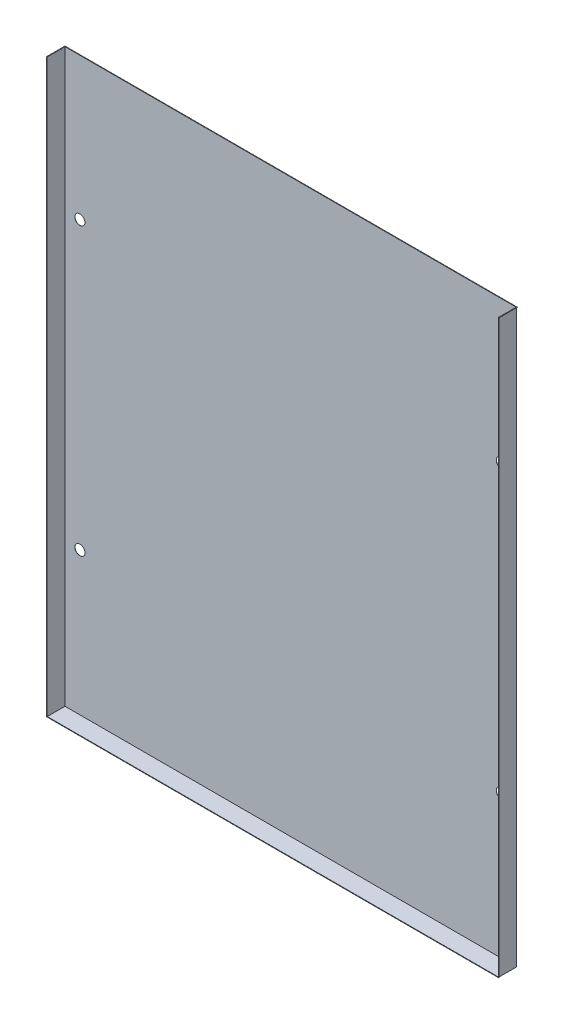
SolidWorks part; units mm, degrees
material "Kapton Film"
ref_plane "Front Plane" through (0, 0, 0) normal (0, 0, 1) x (1, 0, 0)
ref_plane "Top Plane" through (0, 0, 0) normal (0, 1, 0) x (1, 0, 0)
ref_plane "Right Plane" through (0, 0, 0) normal (1, 0, 0) x (0, 0, -1)
sketch "Sketch1" plane through (0, 0, 0) normal (0, 0, 1) x (1, 0, 0)
  line L0 (-83.72, 56.9443) -> (-83.72, -56.7081) construction
  line L1 (-89.6514, -113.4657) -> (89.6514, -113.4657)
  line L2 (-89.6514, -113.4657) -> (-89.6514, 113.4657)
  line L3 (-89.6514, 113.4657) -> (89.6514, 113.4657)
  line L4 (89.6514, -113.4657) -> (89.6514, 113.4657) construction
  line L5 (0, 113.4657) -> (0, -113.4657)
  circle A0 centre (-83.72, 56.9443) radius 2
  circle A1 centre (-83.72, -56.7081) radius 2
  dimension "D3" = 4
  dimension "D4" = 4
  dimension "D1" = 179.3028
  dimension "D2" = 226.9314
  dimension "D5" = 5.9314
  dimension "D6" = 56.7576
  dimension "D7" = 170.41
extrude "Heat Exchanger" add sketch "Sketch1" along normal blind 0.0686 contours L5 L3 L2 L1 region at (-44.7776, -0.0001, 0)
sketch "Sketch3" plane through (0, 0, 0) normal (0, 0, 1) x (1, 0, 0)
  line L3 (0, -113.5343) -> (0, -113.4657)
  line L4 (0, -113.4657) -> (-89.6514, -113.4657)
  line L5 (-89.72, -113.5343) -> (0, -113.5343)
  line L6 (-89.72, 113.4657) -> (-89.72, -113.5343)
  line L7 (-89.72, -113.5343) -> (0, -113.5343)
  line L8 (-89.72, 113.4657) -> (-89.72, -113.5343)
  line L9 (-89.6514, -113.4657) -> (-89.6514, 113.4657)
  line L10 (-89.6514, 113.4657) -> (-89.72, 113.4657)
  dimension "D1" = 0.0686
extrude "Convection Fins" add sketch "Sketch3" along normal blind 7.0524
sketch "Sketch5" plane through (0, 113.4657, 0) normal (0, 1, 0) x (1, 0, 0)
  line L2 (-89.8724, -7.0524) -> (-89.6514, -7.0524)
  line L3 (-89.6514, -7.0524) -> (-89.6514, -0.0686)
  line L4 (-89.8724, 0.1524) -> (0, 0.1524)
  line L5 (-89.8724, -7.0524) -> (-89.8724, 0.1524)
  line L6 (-89.8724, 0.1524) -> (0, 0.1524)
  line L7 (-89.8724, -7.0524) -> (-89.8724, 0.1524)
  line L8 (-89.6514, -0.0686) -> (0, -0.0686)
  line L9 (0, -0.0686) -> (0, 0.1524)
  dimension "D1" = 0.221
extrude "Top Overwrap" add sketch "Sketch5" along normal blind 0.0686
sketch "Sketch7" plane through (0, 0, 7.0524) normal (0, 0, 1) x (1, 0, 0)
  line L3 (-89.8724, 113.5343) -> (-89.6514, 113.5343)
  line L4 (-89.6514, 113.5343) -> (-89.6514, -113.4657)
  line L5 (0, -113.6867) -> (-89.8724, -113.6867)
  line L6 (-89.8724, -113.6867) -> (-89.8724, 113.5343)
  line L7 (0, -113.6867) -> (-89.8724, -113.6867)
  line L8 (-89.8724, -113.6867) -> (-89.8724, 113.5343)
  line L9 (-89.6514, -113.4657) -> (0, -113.4657)
  line L10 (0, -113.4657) -> (0, -113.6867)
  dimension "D1" = 0.221
extrude "Side Overwrap" add sketch "Sketch7" along normal blind 0.0686
mirror "Mirror1" about plane through (0, 0, 0) normal (1, 0, 0) of "Heat Exchanger", "Side Overwrap", "Top Overwrap", "Convection Fins"
